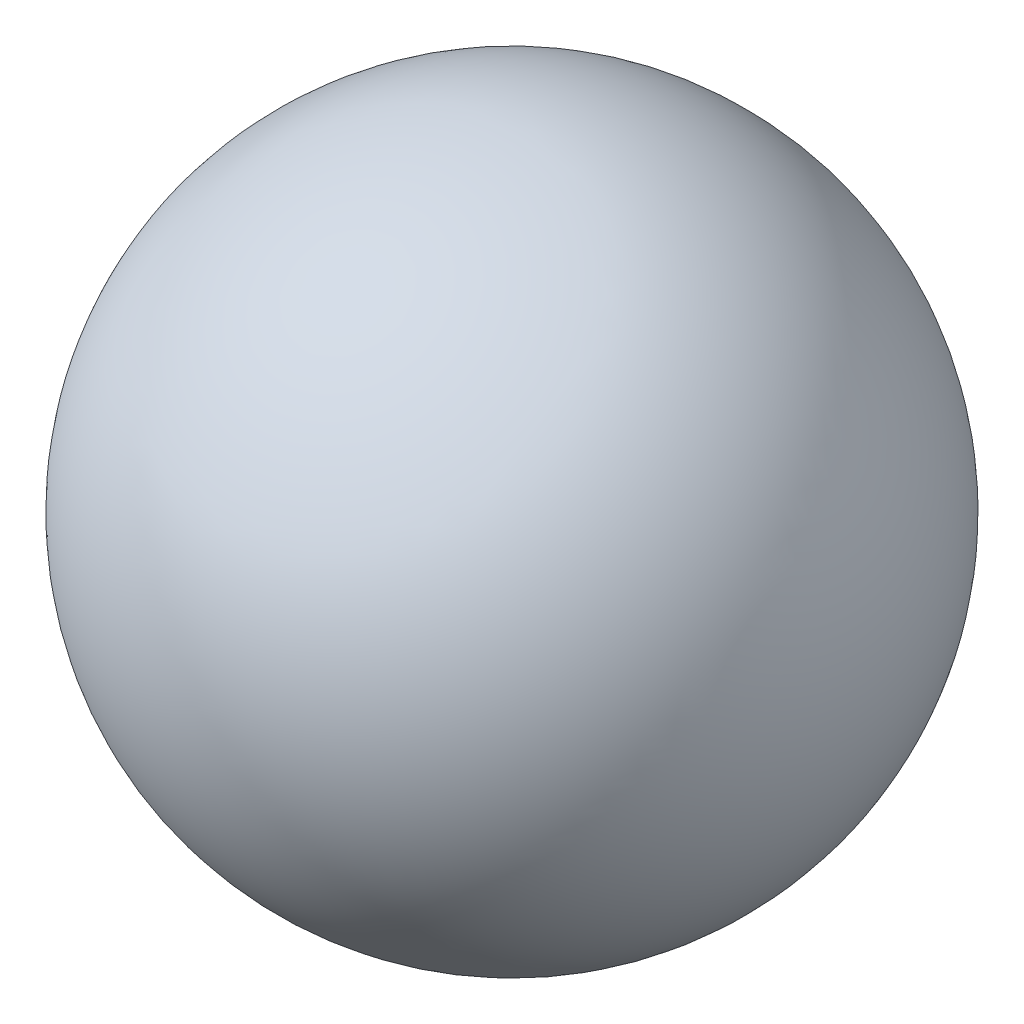
SolidWorks part; units mm, degrees
ref_plane "Front Plane" through (0, 0, 0) normal (0, 0, 1) x (1, 0, 0)
ref_plane "Top Plane" through (0, 0, 0) normal (0, 1, 0) x (1, 0, 0)
ref_plane "Right Plane" through (0, 0, 0) normal (1, 0, 0) x (0, 0, -1)
sketch "Sketch1" plane through (0, 0, 0) normal (0, 0, 1) x (1, 0, 0)
  line L0 (-139.7, 0) -> (139.7, 0)
  arc A0 (-139.7, 0) -> (139.7, 0) centre (0, 0) ccw
  dimension "D1" = 279.4
revolve "Revolve1" add sketch "Sketch1" angle 360 about L0
scale "Scale1" scale about centroid uniform scaling yes scale factor 1.5
